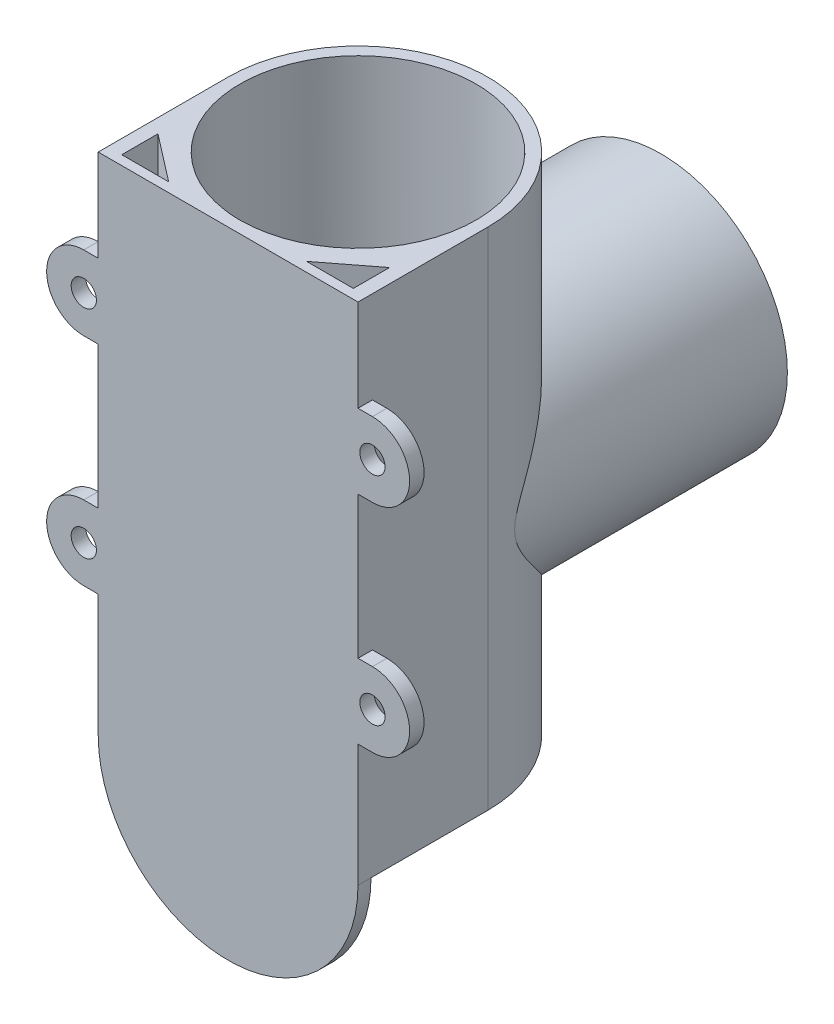
SolidWorks part; units mm, degrees
ref_plane "Front Plane" through (0, 0, 0) normal (0, 0, 1) x (1, 0, 0)
ref_plane "Top Plane" through (0, 0, 0) normal (0, 1, 0) x (1, 0, 0)
ref_plane "Right Plane" through (0, 0, 0) normal (1, 0, 0) x (0, 0, -1)
sketch "Sketch1" plane through (0, 0, 0) normal (0, 1, 0) x (1, 0, 0)
  line L0 (18, -18) -> (-18, -18)
  line L1 (-18, -18) -> (-18, 0)
  line L2 (0, -55) -> (0, 55) construction
  line L3 (18, -18) -> (18, 0)
  line L4 (-16.0462, -16.691) -> (-9.5492, -16.691)
  line L5 (-9.5492, -16.691) -> (-16.0462, -11.6765)
  line L6 (-16.0462, -11.6765) -> (-16.0462, -16.691)
  line L7 (16.0462, -16.691) -> (9.5492, -16.691)
  line L8 (9.5492, -16.691) -> (16.0462, -11.6765)
  line L9 (16.0462, -11.6765) -> (16.0462, -16.691)
  arc A0 (18, 0) -> (-18, 0) centre (0, 0) ccw
  circle A1 centre (0, 0) radius 16.35
  point P10 (0, -18)
  point P16 (0, 0)
  point P17 (0, 0)
  dimension "D1" = 36
  dimension "D2" = 1.65
extrude "Boss-Extrude1" add sketch "Sketch1" along normal blind 70
sketch "Sketch2" plane through (0, 0, 18) normal (0, 0, 1) x (1, 0, 0)
  line L0 (0, -55) -> (0, 55) construction
  circle A0 centre (0, 31.2916) radius 15.24
  point P4 (0, 0)
  point P5 (0, 46.6788)
  point P6 (0, 31.2916)
  dimension "D1" = 30.48
sketch "Sketch4" plane through (0, 0, 18) normal (0, 0, 1) x (1, 0, 0)
  line L0 (-18, 0) -> (18, 0)
  line L1 (-18, 70) -> (-18, 0) construction
  arc A0 (-18, 0) -> (18, 0) centre (0, 0) ccw
extrude "Boss-Extrude3" add sketch "Sketch4" against normal blind 1.8
sketch "Sketch5" plane through (0, 0, 0) normal (1, 0, 0) x (0, 0, -1)
  line L0 (-14.2, 0) -> (-18, -15.9552)
  line L1 (55, 0) -> (-55, 0) construction
  line L2 (-18, 0) -> (-18, -18) construction
  line L3 (-18, -15.9552) -> (-16.2, -18)
  line L4 (-16.2, -18) -> (-14.2, 0)
sketch "Sketch6" plane through (0, 0, 18) normal (0, 0, 1) x (1, 0, 0)
  line L0 (0, -19.8) -> (0, 19.8) construction
  line L5 (-12.2959, 27.2473) -> (-12.2959, 16.9473)
  line L6 (-20, 46.9468) -> (-12.2959, 46.9468)
  line L7 (-20, 57.2478) -> (-12.2959, 57.2478)
  line L8 (-20, 27.2473) -> (-12.2959, 27.2473)
  line L9 (-20, 16.9473) -> (-12.2959, 16.9473)
  line L10 (9.1712, 57.2478) -> (20, 57.2478)
  line L12 (9.1712, 57.2478) -> (9.1712, 46.9468)
  line L14 (-12.2959, 57.2478) -> (-12.2959, 46.9468)
  line L15 (9.1712, 27.2473) -> (9.1712, 16.9473)
  line L19 (9.1712, 46.9468) -> (20, 46.9468)
  line L20 (9.1712, 27.2473) -> (20, 27.2473)
  line L21 (9.1712, 16.9473) -> (20, 16.9473)
  circle A0 centre (-20, 22.0973) radius 1.75
  circle A1 centre (-20, 52.0973) radius 1.75
  circle A2 centre (20, 52.0973) radius 1.75
  circle A3 centre (20, 22.0973) radius 1.75
  arc A4 (-20, 57.2478) -> (-20, 46.9468) centre (-20, 52.0973) ccw
  arc A5 (-20, 27.2473) -> (-20, 16.9473) centre (-20, 22.0973) ccw
  arc A6 (20, 27.2473) -> (20, 16.9473) centre (20, 22.0973) cw
  arc A7 (20, 57.2478) -> (20, 46.9468) centre (20, 52.0973) cw
  point P0 (0, 48.9125)
  point P2 (-3.0515, 44.9806)
  point P13 (-20, 58.9287)
  point P14 (-20, 59.1196)
  point P26 (-20, 52.0973)
  point P28 (0, 0)
  point P31 (9.1712, 46.9468)
  point P32 (0, 0)
  point P33 (0, 0)
  point P35 (0, 0)
  dimension "D5" = 3.5
  dimension "D6" = 3.5
  dimension "D1" = 10.3
  dimension "D8" = 3.5
  dimension "D9" = 3.5
  dimension "D2" = 20
  dimension "D3" = 30
  dimension "D4" = 20
  dimension "D7" = 20
extrude "Boss-Extrude4" add sketch "Sketch6" against normal blind 2
sketch "Sketch8" plane through (0, 0, 0) normal (0, 0, 1) x (1, 0, 0)
  circle A0 centre (0, 31.2916) radius 17.5
  point P4 (0, 0)
  point P5 (0, 46.6788)
  point P6 (0, 31.2916)
  dimension "D1" = 35
extrude "Cut-Extrude4" cut sketch "Sketch2" against normal blind 90 from offset 10 offset against normal yes
extrude "Extrude-Thin1" add sketch "Sketch8" against normal blind 40 from offset 2 thin offset against normal yes thin type one direction reverse wall 2
sketch "Sketch9" plane through (0, 0, 0) normal (0, 1, 0) x (1, 0, 0)
  circle A1 centre (0, 0) radius 16.35
  point P10 (0, -18)
  point P16 (0, 0)
  point P17 (0, 0)
extrude "Cut-Extrude5" cut sketch "Sketch9" against normal through all both and the other way through all
